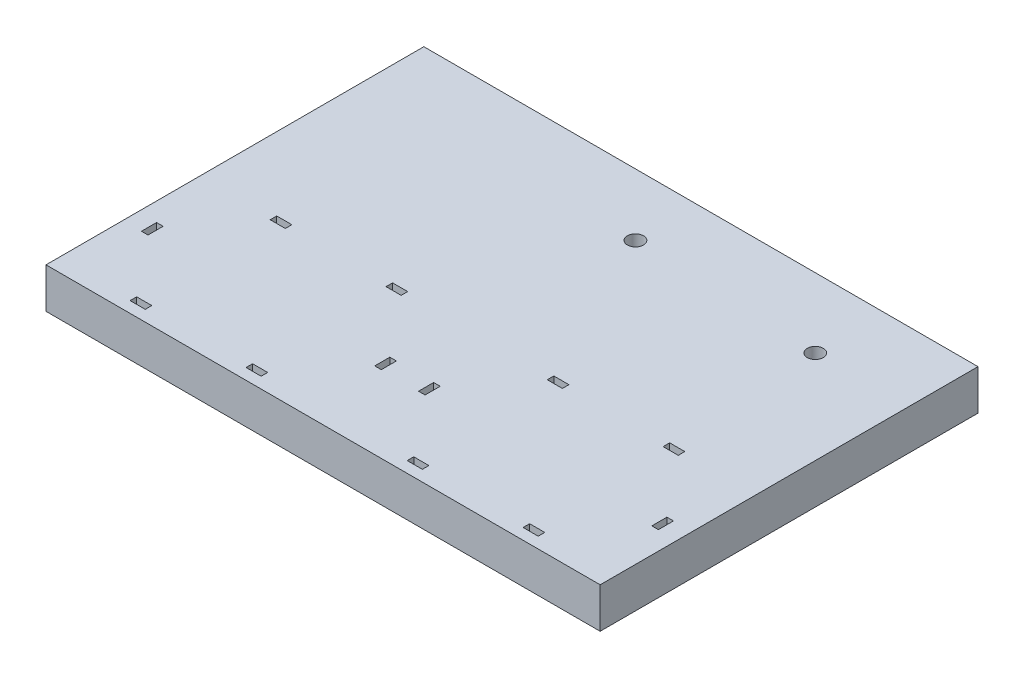
SolidWorks part; units mm, degrees
ref_plane "Front Plane" through (0, 0, 0) normal (0, 0, 1) x (1, 0, 0)
ref_plane "Top Plane" through (0, 0, 0) normal (0, 1, 0) x (1, 0, 0)
ref_plane "Right Plane" through (0, 0, 0) normal (1, 0, 0) x (0, 0, -1)
sketch "Sketch1" plane through (0, 0, 0) normal (0, 1, 0) x (1, 0, 0)
  line L0 (-66.0627, 0) -> (65.2437, 0) construction
  line L1 (-55, 37.5) -> (55, 37.5)
  line L2 (-55, 37.5) -> (-55, -37.5)
  line L3 (-55, -37.5) -> (55, -37.5)
  line L4 (55, 37.5) -> (55, -37.5)
  line L5 (27.5, -7.5) -> (27.5, -34) construction
  line L6 (40, 10) -> (-23.5, 10) construction
  line L7 (40, 10) -> (40, 35) construction
  line L8 (40, 35) -> (-23.5, 35) construction
  line L9 (-23.5, 10) -> (-23.5, 35) construction
  line L10 (5, -7.5) -> (50, -7.5) construction
  line L11 (5, -7.5) -> (5, -34) construction
  line L12 (5, -34) -> (50, -34) construction
  line L13 (50, -7.5) -> (50, -34) construction
  line L14 (5, -20.75) -> (50, -20.75) construction
  line L15 (40.5, -7.5) -> (37.5, -7.5)
  line L16 (14.5, -7.5) -> (17.5, -7.5)
  line L17 (14.5, -7.5) -> (14.5, -6.2)
  line L18 (14.5, -6.2) -> (17.5, -6.2)
  line L19 (17.5, -7.5) -> (17.5, -6.2)
  line L20 (5, -19.25) -> (3.7, -19.25)
  line L21 (5, -19.25) -> (5, -22.25)
  line L22 (5, -22.25) -> (3.7, -22.25)
  line L23 (3.7, -19.25) -> (3.7, -22.25)
  line L24 (37.5, -7.5) -> (37.5, -6.2)
  line L25 (40.5, -6.2) -> (37.5, -6.2)
  line L26 (40.5, -7.5) -> (40.5, -6.2)
  line L27 (50, -19.25) -> (51.3, -19.25)
  line L28 (51.3, -19.25) -> (51.3, -22.25)
  line L29 (50, -22.25) -> (51.3, -22.25)
  line L30 (50, -19.25) -> (50, -22.25)
  line L31 (37.5, -34) -> (37.5, -35.3)
  line L32 (40.5, -34) -> (37.5, -34)
  line L33 (40.5, -34) -> (40.5, -35.3)
  line L34 (40.5, -35.3) -> (37.5, -35.3)
  line L35 (14.5, -34) -> (17.5, -34)
  line L36 (17.5, -34) -> (17.5, -35.3)
  line L37 (14.5, -34) -> (14.5, -35.3)
  line L38 (14.5, -35.3) -> (17.5, -35.3)
  line L39 (0, -65.1553) -> (0, 67.8606) construction
  line L46 (-14.5, -35.3) -> (-17.5, -35.3)
  line L47 (-14.5, -34) -> (-14.5, -35.3)
  line L48 (-17.5, -34) -> (-17.5, -35.3)
  line L49 (-14.5, -34) -> (-17.5, -34)
  line L50 (-40.5, -35.3) -> (-37.5, -35.3)
  line L51 (-40.5, -34) -> (-40.5, -35.3)
  line L52 (-40.5, -34) -> (-37.5, -34)
  line L53 (-37.5, -34) -> (-37.5, -35.3)
  line L54 (-50, -19.25) -> (-50, -22.25)
  line L55 (-50, -22.25) -> (-51.3, -22.25)
  line L56 (-51.3, -19.25) -> (-51.3, -22.25)
  line L57 (-50, -19.25) -> (-51.3, -19.25)
  line L58 (-40.5, -7.5) -> (-40.5, -6.2)
  line L59 (-40.5, -6.2) -> (-37.5, -6.2)
  line L60 (-37.5, -7.5) -> (-37.5, -6.2)
  line L61 (-3.7, -19.25) -> (-3.7, -22.25)
  line L62 (-5, -22.25) -> (-3.7, -22.25)
  line L63 (-5, -19.25) -> (-5, -22.25)
  line L64 (-5, -19.25) -> (-3.7, -19.25)
  line L65 (-17.5, -7.5) -> (-17.5, -6.2)
  line L66 (-14.5, -6.2) -> (-17.5, -6.2)
  line L67 (-14.5, -7.5) -> (-14.5, -6.2)
  line L68 (-14.5, -7.5) -> (-17.5, -7.5)
  line L69 (-40.5, -7.5) -> (-37.5, -7.5)
  circle A0 centre (36.5, 23.7) radius 1.6
  circle A1 centre (-0.7, 25.2) radius 1.6
  point P4 (55, 0)
  point P6 (0, 37.5)
  point P33 (5, -20.75)
  point P52 (0, -37.5)
  dimension "D5" = 3.2
  dimension "D10" = 3.2
  dimension "D17" = 3
  dimension "D18" = 1.3
  dimension "D1" = 110
  dimension "D2" = 75
  dimension "D3" = 10
  dimension "D4" = 15
  dimension "D6" = 3.5
  dimension "D7" = 13.7
  dimension "D8" = 63.5
  dimension "D9" = 25
  dimension "D11" = 40.7
  dimension "D12" = 15.2
  dimension "D13" = 26.5
  dimension "D14" = 45
  dimension "D15" = 7.5
  dimension "D16" = 5
  dimension "D19" = 3
  dimension "D20" = 1.3
  dimension "D21" = 20
extrude "Boss-Extrude1" add sketch "Sketch1" along normal blind 8
